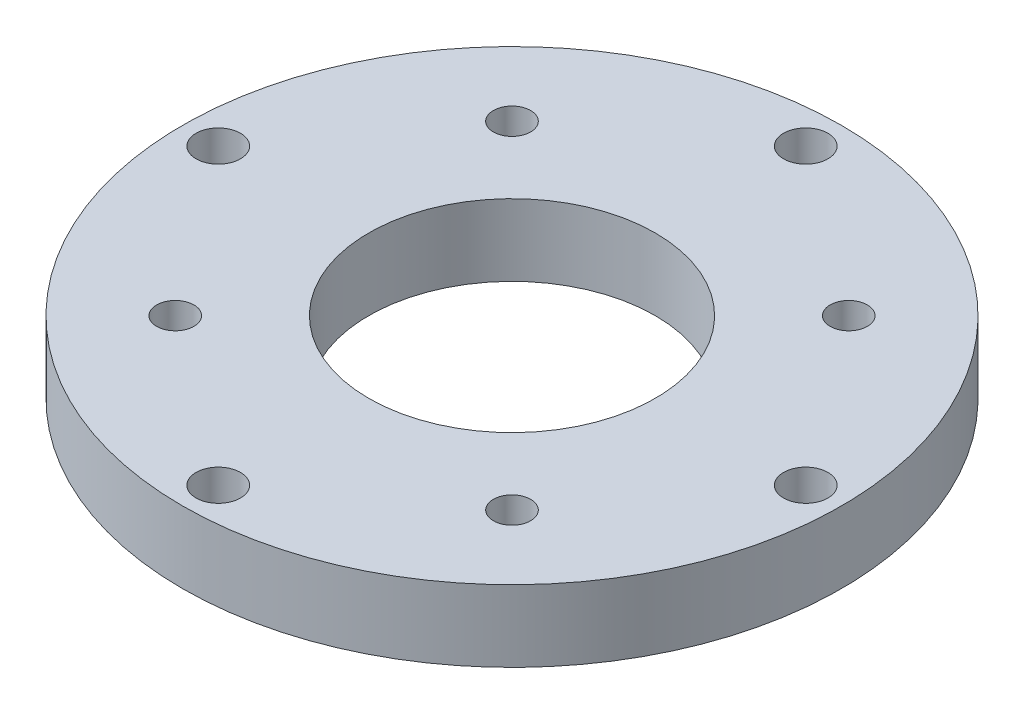
SolidWorks part; units mm, degrees
ref_plane "前视基准面" through (0, 0, 0) normal (0, 0, 1) x (1, 0, 0)
ref_plane "上视基准面" through (0, 0, 0) normal (0, 1, 0) x (1, 0, 0)
ref_plane "右视基准面" through (0, 0, 0) normal (1, 0, 0) x (0, 0, -1)
other "Configuration Table"
sketch "草图1" plane through (0, 0, 0) normal (0, 1, 0) x (1, 0, 0)
  line L0 (0, 46) -> (0, -46) construction
  line L1 (-46, 0) -> (46, 0) construction
  line L2 (0, 0) -> (-32.5269, 32.5269) construction
  line L3 (0, 0) -> (32.5269, 32.5269) construction
  line L5 (-19.45, 21.1617) -> (-19.45, 25.8383)
  line L6 (-19.45, 25.8383) -> (-23.5, 28.1765)
  line L7 (-23.5, 28.1765) -> (-27.55, 25.8383)
  line L8 (-27.55, 25.8383) -> (-27.55, 21.1617)
  line L9 (-27.55, 21.1617) -> (-23.5, 18.8235)
  line L10 (-23.5, 18.8235) -> (-19.45, 21.1617)
  line L52 (21.1617, 19.45) -> (25.8383, 19.45)
  line L53 (25.8383, 19.45) -> (28.1765, 23.5)
  line L54 (28.1765, 23.5) -> (25.8383, 27.55)
  line L55 (25.8383, 27.55) -> (21.1617, 27.55)
  line L56 (21.1617, 27.55) -> (18.8235, 23.5)
  line L57 (18.8235, 23.5) -> (21.1617, 19.45)
  line L58 (19.45, -21.1617) -> (19.45, -25.8383)
  line L59 (19.45, -25.8383) -> (23.5, -28.1765)
  line L60 (23.5, -28.1765) -> (27.55, -25.8383)
  line L61 (27.55, -25.8383) -> (27.55, -21.1617)
  line L62 (27.55, -21.1617) -> (23.5, -18.8235)
  line L63 (23.5, -18.8235) -> (19.45, -21.1617)
  line L64 (-21.1617, -19.45) -> (-25.8383, -19.45)
  line L65 (-25.8383, -19.45) -> (-28.1765, -23.5)
  line L66 (-28.1765, -23.5) -> (-25.8383, -27.55)
  line L67 (-25.8383, -27.55) -> (-21.1617, -27.55)
  line L68 (-21.1617, -27.55) -> (-18.8235, -23.5)
  line L69 (-18.8235, -23.5) -> (-21.1617, -19.45)
  line L70 (0, 0) -> (-19.45, 21.1617) construction
  line L71 (0, 0) -> (0, 41) construction
  circle A0 centre (0, 0) radius 46
  circle A1 centre (0, 0) radius 20
  circle A10 centre (-23.5, 23.5) radius 2.6
  circle A11 centre (23.5, 23.5) radius 2.6
  circle A12 centre (23.5, -23.5) radius 2.6
  circle A13 centre (-23.5, -23.5) radius 2.6
  circle A18 centre (-23.5, 23.5) radius 4.05 construction
  circle A19 centre (0, 41) radius 3.1
  circle A20 centre (41, 0) radius 3.1
  circle A21 centre (0, -41) radius 3.1
  circle A22 centre (-41, 0) radius 3.1
  dimension "D1" = 92
  dimension "D2" = 40
  dimension "D4" = 45
  dimension "D7" = 47
  dimension "D6" = 5.2
  dimension "D8" = 4
  dimension "D10" = 6.2
  dimension "D3" = 45
  dimension "D5" = 8.1
  dimension "D9" = 28.7423
  dimension "D11" = 41
  dimension "D13" = 41
  dimension "D12" = 4
extrude "凸台-拉伸1" add sketch "草图1" along normal blind 4 contours A0 A1 L10 L9 L8 L7 L6 L5 L68 L67 L66 L65 region at (-44.6989, 0, 0)
extrude "凸台-拉伸3" add sketch "草图1<8>" along normal blind 6 from surface contours L9 L10 L5 L6 L7 L8 A10 | L56 L57 L52 L53 L54 L55 A11 | L62 L63 L58 L59 L60 L61 A12 | L68 L69 L64 L65 L66 L67 A13 | A0 A22 A21 A20 A19 A1 L10 L9 L8 L7 L6 L5 L57 L56 L55 L54 L53 L52 L63 L62 L61 L60 L59 L58 L69 L68 L67 L66 L65 L64 region at (-21.5369, 0, -20.0998) region at (20.0998, 0, -21.5369) region at (21.5369, 0, 20.0998) region at (-20.0998, 0, 21.5369) region at (-44.6989, 0, 0) starting at face at (-41, 4, 3.1)
sketch "草图1<8>" plane through (0, 0, 0) normal (0, 1, 0) x (1, 0, 0) same geometry as "草图1"
